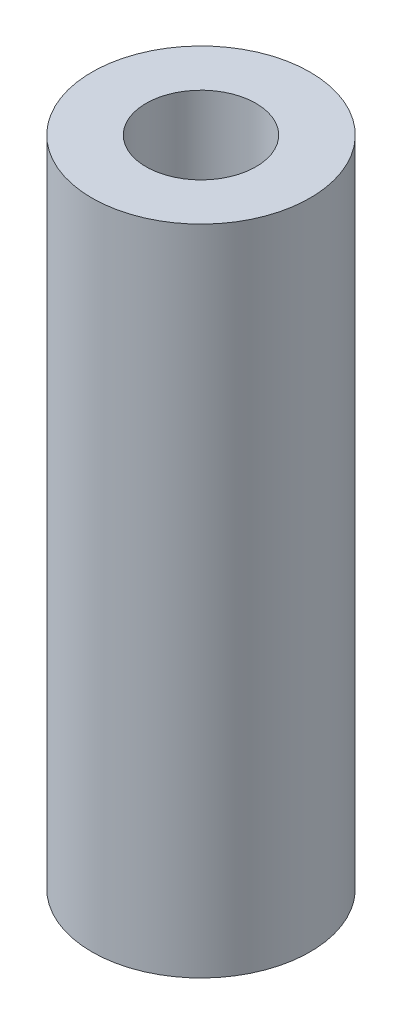
SolidWorks part; units mm, degrees
material "ABS PC"
ref_plane "Front" through (0, 0, 0) normal (0, 0, 1) x (1, 0, 0)
ref_plane "Top" through (0, 0, 0) normal (0, 1, 0) x (1, 0, 0)
ref_plane "Right" through (0, 0, 0) normal (1, 0, 0) x (0, 0, -1)
sketch "Sketch1" plane through (0, 0, 0) normal (0, 1, 0) x (1, 0, 0)
  circle A0 centre (0, 0) radius 4.7625
  circle A1 centre (0, 0) radius 2.4
  dimension "D1" = 9.525
  dimension "D2" = 4.8
extrude "Boss-Extrude1" add sketch "Sketch1" along normal mid plane 28.5
